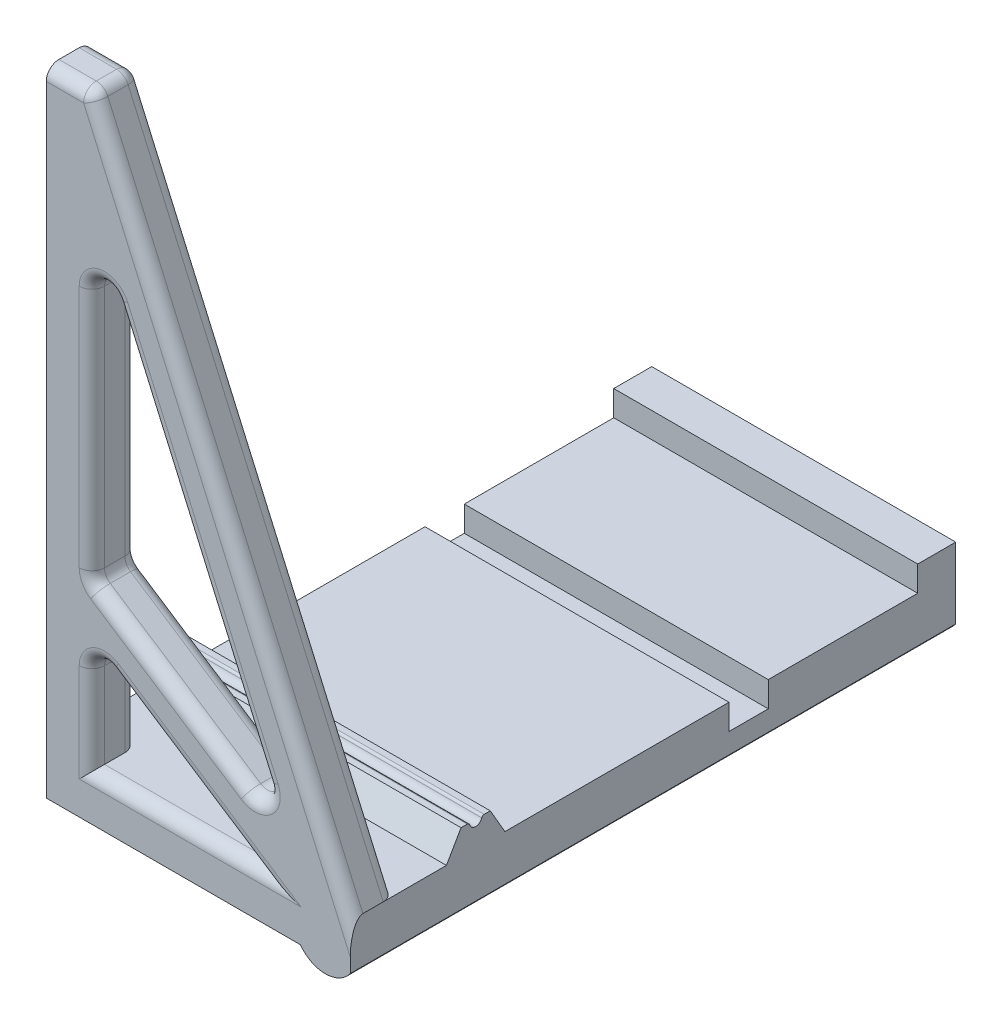
SolidWorks part; units mm, degrees
ref_plane "前基準面" through (0, 0, 0) normal (0, 0, 1) x (1, 0, 0)
ref_plane "上基準面" through (0, 0, 0) normal (0, 1, 0) x (1, 0, 0)
ref_plane "右基準面" through (0, 0, 0) normal (1, 0, 0) x (0, 0, -1)
sketch "草圖1" plane through (0, 0, 0) normal (1, 0, 0) x (0, 0, -1)
  line L0 (-179.6667, 241.3333) -> (-179.6667, -8.6667)
  line L1 (-179.6667, -8.6667) -> (59.3333, -8.6667)
  line L2 (59.3333, -8.6667) -> (59.3333, 9.3333)
  line L3 (44.3333, 9.3333) -> (-161.6667, 9.3333)
  line L4 (-161.6667, 9.3333) -> (-161.6667, 241.3333)
  line L5 (-161.6667, 241.3333) -> (-179.6667, 241.3333)
  line L8 (59.3333, 9.3333) -> (59.3333, 19.3333)
  line L9 (59.3333, 19.3333) -> (44.3333, 19.3333)
  line L10 (44.3333, 9.3333) -> (44.3333, 19.3333)
  dimension "D1" = 250
  dimension "D2" = 239
  dimension "D3" = 18
  dimension "D4" = 18
  dimension "D5" = 10
  dimension "D6" = 15
  dimension "D7" = 18
extrude "填料-伸長1" add sketch "草圖1" along normal blind 120
sketch "草圖2" plane through (120, 0, 0) normal (1, 0, 0) x (0, 0, -1)
  line L0 (-30.1667, 9.3333) -> (-30.1667, -0.6667)
  line L1 (-30.1667, -0.6667) -> (-14.6667, -0.6667)
  line L2 (-14.6667, -0.6667) -> (-14.6667, 9.3333)
  line L3 (-14.6667, 9.3333) -> (-30.1667, 9.3333)
  line L4 (44.3333, 9.3333) -> (-161.6667, 9.3333) construction
  line L5 (59.3333, -8.6667) -> (59.3333, 19.3333) construction
  dimension "D1" = 15.5
  dimension "D2" = 10
  dimension "D3" = 0
  dimension "D4" = 74
extrude "除料-伸長1" cut sketch "草圖2" against normal through all
sketch "草圖3" plane through (0, 0, 179.6667) normal (0, 0, 1) x (1, 0, 0)
  line L0 (120, -8.6667) -> (120, 9.3333)
  line L1 (120, 241.3333) -> (120, -8.6667) construction
  dimension "D1" = 18
sketch "草圖4" plane through (0, 0, 179.6667) normal (0, 0, 1) x (1, 0, 0)
  line L0 (0, 241.3333) -> (18, 241.3333)
  line L1 (120, 241.3333) -> (0, 241.3333) construction
  line L2 (18, 241.3333) -> (120, 9.3333)
  line L3 (120, 9.3333) -> (120, 241.3333)
  line L4 (120, 241.3333) -> (18, 241.3333)
  line M3 (120, -8.6667) -> (120, 241.3333)
  line M4 (120, 241.3333) -> (0, 241.3333)
  dimension "D1" = 18
extrude "除料-伸長2" cut sketch "草圖4" against normal blind 40 contours L2 M4 M3 region at (86, 164, 179.6667)
sketch "草圖5" plane through (0, 0, 179.6667) normal (0, 0, 1) x (1, 0, 0)
  line L0 (10.3776, 213.9472) -> (100.3371, 9.3333)
  line L1 (18, 241.3333) -> (120, 9.3333) construction
  line L2 (18, 197.6408) -> (18, 9.3333)
  line L3 (0, 241.3333) -> (0, -8.6667) construction
  line L4 (18, 9.3333) -> (100.3371, 9.3333)
  line L5 (120, -8.6667) -> (0, -8.6667) construction
  point P4 (36, 155.6688)
  point P10 (10.3776, 213.9472)
  dimension "D1" = 18
  dimension "D2" = 18
  dimension "D3" = 18
  dimension "D4" = 18
extrude "除料-伸長3" cut sketch "草圖5" against normal blind 40 contours L2 L4 L0 region at (45.4457, 71.7589, 179.6667)
fillet "圓角16" radius 5 5 edges at (69, 125.3333, 161.6667) (69, 125.3333, 179.6667) (9, 241.3333, 161.6667) (18, 241.3333, 170.6667) (9, 241.3333, 179.6667)
sketch "草圖8" plane through (0, 0, 179.6667) normal (0, 0, 1) x (1, 0, 0)
  line L0 (120, -8.6667) -> (100.34, -8.6667)
  line L1 (120, -8.6667) -> (0, -8.6667) construction
  line L2 (100.34, -8.6667) -> (100.34, -3.6667)
  line L3 (100.34, -3.6667) -> (120, -3.6667)
  line L4 (100.34, -8.6667) -> (120, -8.6667)
  line L5 (120, -3.6667) -> (120, -8.6667)
  line L6 (100.3371, 9.3333) -> (120, 9.3333)
  line L7 (120, 9.3333) -> (120, -8.6667)
  line L8 (110.17, -8.6667) -> (110.17, -13.6667) construction
  arc A0 (120, -8.6667) -> (100.34, -8.6667) centre (110.17, -1.5038) cw
  line M9 (0, -8.6667) -> (120, -8.6667)
  dimension "D4" = 5
  dimension "D1" = 19.66
  dimension "D2" = 5
  dimension "D3" = 19.66
extrude "填料-伸長2" add sketch "草圖8" against normal blind 239 contours L8 A0 M9 | L4 L8 A0 region at (113.9836, -10.7067, 179.6667) region at (106.3564, -10.7067, 179.6667)
sketch "草圖9" plane through (0, 0, 179.6667) normal (0, 0, 1) x (1, 0, 0)
  line L0 (83.8721, 9.3333) -> (100.3371, 9.3333)
  line L1 (100.3371, 9.3333) -> (93.7099, 24.4071)
  line L3 (18, 73.8277) -> (18, 52.3322)
  line L4 (100.3371, 9.3333) -> (18, 63.0799) construction
  line L5 (18, 63.0799) -> (13.0805, 55.5435)
  line L6 (105.2567, 16.8698) -> (95.4176, 1.7969)
  line L7 (13.0805, 55.5435) -> (95.4176, 1.7969)
  line L8 (22.9195, 70.6164) -> (105.2567, 16.8698)
  line L9 (93.7112, 24.4063) -> (100.3371, 9.3333)
  line L10 (18, 63.0799) -> (10.4635, 67.9995)
  line L11 (10.4635, 67.9995) -> (15.3831, 75.5359)
  line L12 (15.3831, 75.5359) -> (22.9195, 70.6164)
  line M11 (18, 9.3333) -> (18, 196.61)
  line M13 (18, 196.61) -> (100.3371, 9.3333)
  line M14 (100.3371, 9.3333) -> (18, 9.3333)
  dimension "D1" = 33.135
  dimension "D2" = 9
  dimension "D3" = 90
  dimension "D4" = 90
  dimension "D5" = 9
  dimension "D6" = 9
  dimension "D7" = 9
  dimension "D8" = 90
extrude "填料-伸長3" add sketch "草圖9" against normal blind 18 contours L4 L8 L12 L3 M13 | L4 L7 M14 M11 | L7 L6 M14 | L8 L9 L6 | L12 L11 L10 L3 | L5 L7 M11 | L5 L7 L6 L8 L12 L11 L10 region at (55.2047, 33.6192, 179.6667) region at (93.209, 6.8212, 179.6667) region at (57.5349, 42.5718, 179.6667) region at (99.7683, 16.8698, 179.6667) region at (16.3602, 56.9852, 179.6667) region at (15.263, 69.3725, 179.6667)
fillet "圓角17" radius 5 15 edges at (55.8549, 110.5085, 161.6667) (50.9361, 30.8328, 161.6667) (18, 30.8328, 161.6667) (18, 135.2188, 161.6667) (18, 135.2188, 179.6667) (55.8549, 110.5085, 179.6667) (55.8549, 49.1174, 161.6667) (55.8549, 49.1174, 179.6667) (18, 30.8328, 179.6667) (50.9361, 30.8328, 179.6667) (50.9361, 9.3333, 179.6667) (18, 196.61, 170.6667) (93.7099, 24.4071, 170.6667) (18, 73.8277, 170.6667) (18, 52.3322, 170.6667)
sketch "草圖10" plane through (120, 0, 0) normal (1, 0, 0) x (0, 0, -1)
  line L0 (-30.1667, 9.3333) -> (-166.6667, 9.3333) construction
  line L1 (-118.6197, 9.3333) -> (-124.3932, 19.3333)
  line L2 (-124.3932, 19.3333) -> (-135.9402, 19.3333)
  line L3 (-135.9402, 19.3333) -> (-141.7137, 9.3333)
  line L4 (-141.7137, 9.3333) -> (-135.9402, -0.6667)
  line L5 (-135.9402, -0.6667) -> (-124.3932, -0.6667)
  line L6 (-124.3932, -0.6667) -> (-118.6197, 9.3333)
  line L8 (-30.1667, 9.3333) -> (-30.1667, -0.6667) construction
  circle A0 centre (-130.1667, 9.3333) radius 10 construction
  dimension "D1" = 20
  dimension "D2" = 100
extrude "填料-伸長4" add sketch "草圖10" against normal blind 120
sketch "草圖11" plane through (0, 0, 0) normal (-1, 0, 0) x (0, 0, 1)
  line L0 (179.6667, -8.6667) -> (-59.3333, -8.6667) construction
  line L1 (-59.3333, -8.6667) -> (179.6667, -8.6667) construction
  line L2 (-59.3333, -8.6667) -> (-59.3333, 19.3333) construction
  circle A0 centre (140.6667, -8.6667) radius 2.5
  circle A1 centre (90.6667, -8.6667) radius 2.5
  circle A2 centre (40.6667, -8.6667) radius 2.5
  circle A3 centre (-9.3333, -8.6667) radius 2.5
  point P12 (0, 0)
  point P14 (0, 0)
  dimension "D1" = 5
  dimension "D2" = 5
  dimension "D3" = 5
  dimension "D4" = 5
  dimension "D5" = 50
  dimension "D6" = 50
  dimension "D7" = 50
  dimension "D8" = 50
extrude "填料-伸長5" add sketch "草圖11" against normal blind 110
sketch "草圖12" plane through (120, 0, 0) normal (1, 0, 0) x (0, 0, -1)
  line L0 (-124.3932, 19.3333) -> (-135.9402, 19.3333) construction
  circle A0 centre (-130.1682, 19.3333) radius 2.5
  dimension "D1" = 5.775
  dimension "D2" = 5
extrude "除料-伸長4" cut sketch "草圖12" against normal through all
fillet "圓角19" radius 1 2 edges at (60, 19.3333, 127.6682) (60, 19.3333, 132.6682)
